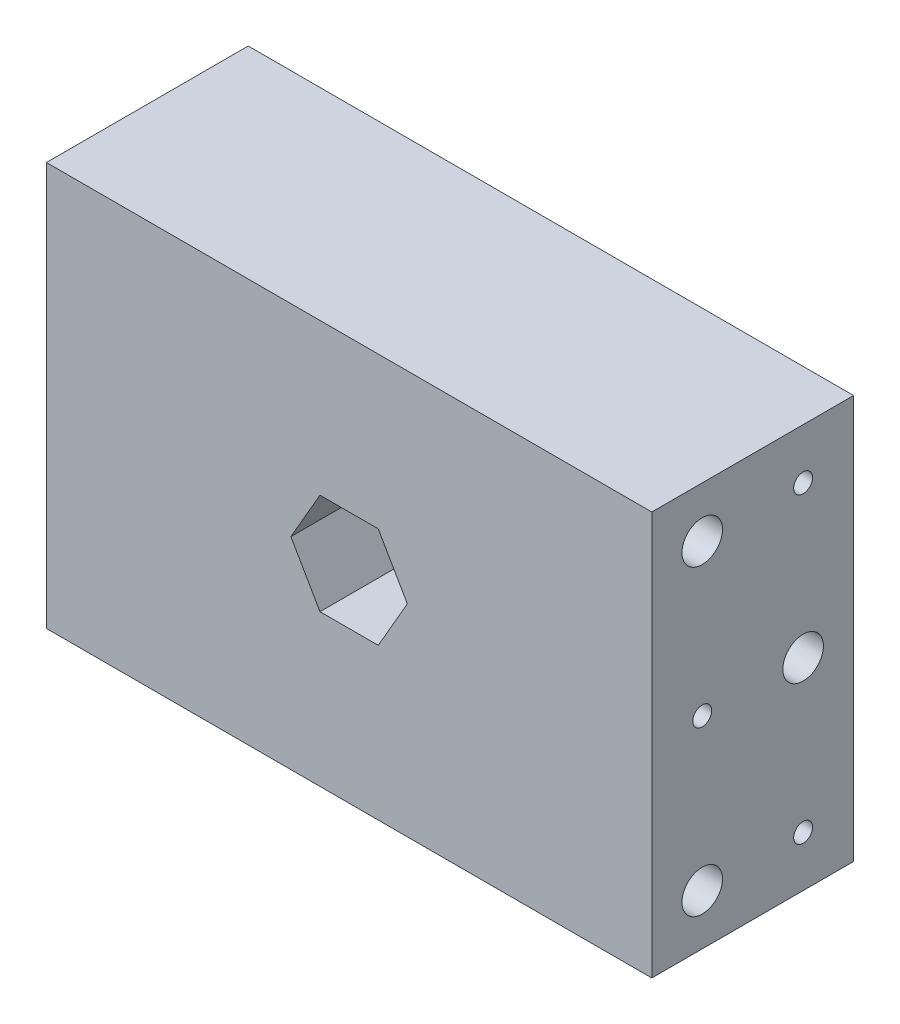
SolidWorks part; units mm, degrees
ref_plane "Front Plane" through (0, 0, 0) normal (0, 0, 1) x (1, 0, 0)
ref_plane "Top Plane" through (0, 0, 0) normal (0, 1, 0) x (1, 0, 0)
ref_plane "Right Plane" through (0, 0, 0) normal (1, 0, 0) x (0, 0, -1)
sketch "Sketch2" plane through (0, 0, 0) normal (0, 0, 1) x (1, 0, 0)
  line L0 (-38.1, -25.4) -> (-38.1, 25.4)
  line L1 (-38.1, 25.4) -> (38.1, 25.4)
  line L3 (38.1, 25.4) -> (-38.1, 25.4)
  line L4 (38.1, 25.4) -> (38.1, -25.4)
  line L5 (38.1, -25.4) -> (-38.1, -25.4)
  line L6 (-38.1, 25.4) -> (-38.1, -25.4)
  line L7 (38.1, 25.4) -> (-38.1, -25.4) construction
  line L8 (38.1, -25.4) -> (-38.1, 25.4) construction
  point P5 (0, 0)
  dimension "D1" = 50.8
  dimension "D2" = 76.2
extrude "Boss-Extrude1" add sketch "Sketch2" along normal blind 25.4 contours L5 L4 L1 L0 region at (0, 0, 0)
sketch "Sketch4" plane through (0, 0, 0) normal (0, 0, -1) x (-1, 0, 0)
  line L2 (3.6662, 6.35) -> (-3.6662, 6.35)
  line L3 (-3.6662, 6.35) -> (-7.3323, 0)
  line L4 (-7.3323, 0) -> (-3.6662, -6.35)
  line L5 (-3.6662, -6.35) -> (3.6662, -6.35)
  line L6 (3.6662, -6.35) -> (7.3323, 0)
  line L7 (7.3323, 0) -> (3.6662, 6.35)
  circle A4 centre (0, 0) radius 6.35 construction
  dimension "D1" = 12.7
hole_wizard "Tap Drill for 1/4-20 Tap1" positions "Sketch5" profile "Sketch6" hole size "1/4-20" standard "ANSI Inch"
sketch "Sketch5" plane through (-38.1, 0, 0) normal (-1, 0, 0) x (0, 0, 1)
  line L0 (25.4, -25.4) -> (25.4, 25.4) construction
  line L1 (0, -25.4) -> (0, 25.4) construction
  line L2 (25.4, -25.4) -> (0, -25.4) construction
  line L3 (25.4, 25.4) -> (0, 25.4) construction
  point P0 (19.05, 19.05)
  point P2 (6.35, 0)
  point P4 (19.05, -19.05)
  dimension "D1" = 6.35
  dimension "D2" = 6.35
  dimension "D3" = 6.35
  dimension "D4" = 6.35
sketch "Sketch6" plane through (-38.1, 19.05, 19.05) normal (0, 1, 0) x (0, 0, 1)
  line L0 (0, 0) -> (0, 20.5838)
  line L1 (0, 20.5838) -> (2.5527, 19.05)
  line L2 (2.5527, 19.05) -> (2.5527, 0)
  line L5 (2.5527, 0) -> (0, 0)
  line L10 (0, 20.5838) -> (-2.5527, 19.05) construction
  line L11 (0, -6.35) -> (0, 107.95) construction
  dimension "Hole Dia." = 5.1054
  dimension "Hole Depth" = 19.05
  dimension "Drill Angle" = 118
hole_wizard "3/32 (0.09375) Dowel Hole1" positions "Sketch7" profile "Sketch8" hole size "3/32" standard "ANSI Inch"
sketch "Sketch7" plane through (-38.1, 0, 0) normal (-1, 0, 0) x (0, 0, 1)
  point P0 (6.35, 19.05)
  point P2 (6.35, -19.05)
  point P4 (19.05, 0)
sketch "Sketch8" plane through (-38.1, 19.05, 6.35) normal (0, 1, 0) x (0, 0, 1)
  line L0 (0, 0) -> (0, 8.6529)
  line L1 (0, 8.6529) -> (1.1906, 7.9375)
  line L2 (1.1906, 7.9375) -> (1.1906, 0)
  line L5 (1.1906, 0) -> (0, 0)
  line L10 (0, 8.6529) -> (-1.1906, 7.9375) construction
  line L11 (0, -6.35) -> (0, 107.95) construction
  dimension "Hole Dia." = 2.3812
  dimension "Hole Depth" = 7.9375
  dimension "Drill Angle" = 118
mirror "Mirror1" about plane through (0, 0, 0) normal (1, 0, 0) of "3/32 (0.09375) Dowel Hole1", "Tap Drill for 1/4-20 Tap1"
extrude "Cut-Extrude1" cut sketch "Sketch4" against normal through all
ref_axis "Axis1" through (0, 0, 26.67) along (0, 0, -1)
